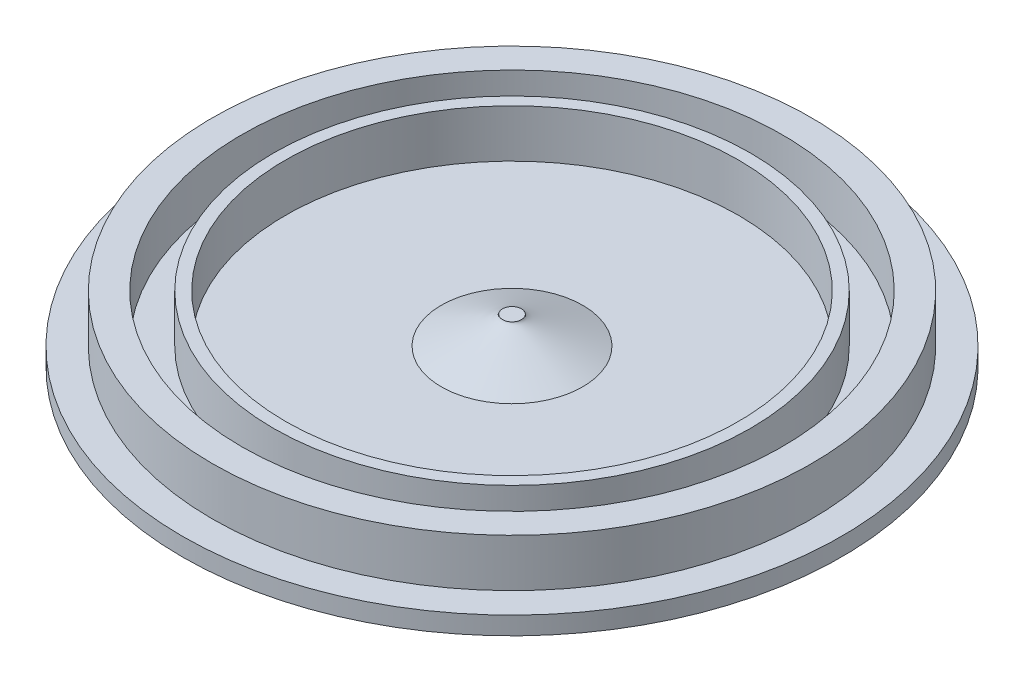
SolidWorks part; units mm, degrees
ref_plane "Front Plane" through (0, 0, 0) normal (0, 0, 1) x (1, 0, 0)
ref_plane "Top Plane" through (0, 0, 0) normal (0, 1, 0) x (1, 0, 0)
ref_plane "Right Plane" through (0, 0, 0) normal (1, 0, 0) x (0, 0, -1)
sketch "Sketch1" plane through (0, 0, 0) normal (0, 1, 0) x (1, 0, 0)
  circle A0 centre (0, 0) radius 69.85
  dimension "D1" = 139.7
extrude "Boss-Extrude1" add sketch "Sketch1" along normal blind 3.81
sketch "Sketch2" plane through (0, 3.81, 0) normal (0, 1, 0) x (1, 0, 0)
  circle A0 centre (0, 0) radius 63.5
  circle A1 centre (0, 0) radius 57.2897
  dimension "D1" = 127
  dimension "D2" = 114.5794
extrude "Boss-Extrude2" add sketch "Sketch2" along normal blind 10.16
sketch "Sketch3" plane through (0, 3.81, 0) normal (0, 1, 0) x (1, 0, 0)
  circle A0 centre (0, 0) radius 50.546
  circle A1 centre (0, 0) radius 48.006
  dimension "D1" = 101.092
  dimension "D2" = 96.012
extrude "Boss-Extrude3" add sketch "Sketch3" along normal blind 10.16
sketch "Sketch4" plane through (0, 3.81, 0) normal (0, 1, 0) x (1, 0, 0)
  circle A0 centre (0, 0) radius 14.986
  dimension "D1" = 29.972
ref_plane "Plane1" through (0, 9.652, 0) normal (0, 1, 0) x (1, 0, 0)
sketch "Sketch5" plane through (0, 9.652, 0) normal (0, 1, 0) x (1, 0, 0)
  circle A0 centre (0, 0) radius 1.9939
  dimension "D1" = 3.9878
loft "Loft1" add profiles "Sketch5", "Sketch4" connector at (-1.8157, 9.652, 0.8239) connector at (4.2532, 3.81, 14.3698)
sketch "Sketch6" plane through (0, 0, 0) normal (0, -1, 0) x (1, 0, 0)
  circle A0 centre (0, 0) radius 127
  dimension "D1" = 254
